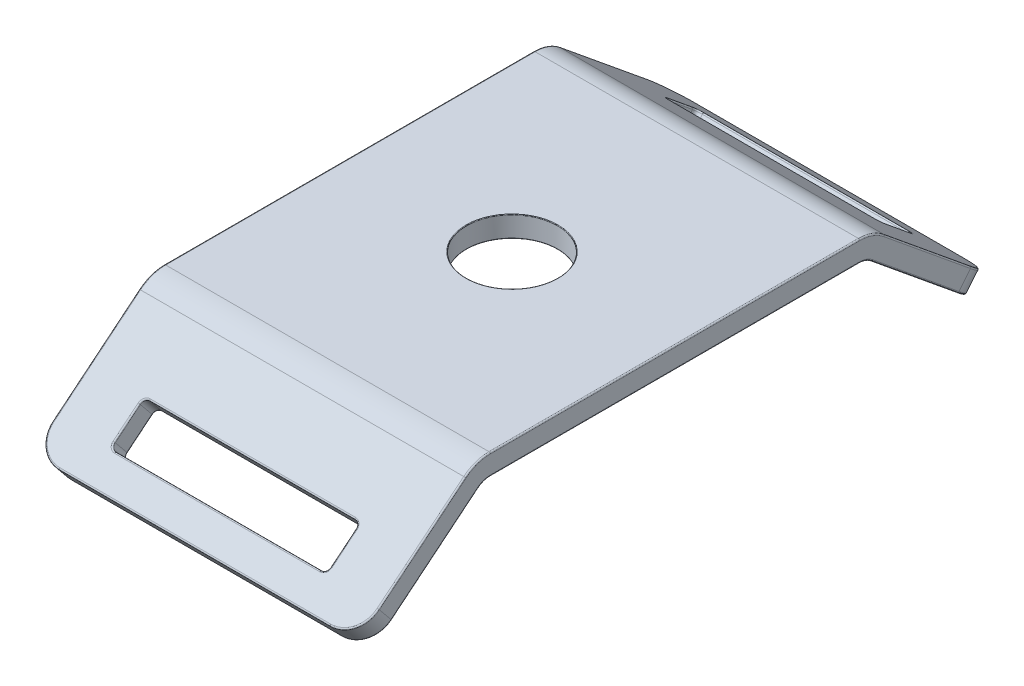
SolidWorks part; units mm, degrees
ref_plane "Front Plane" through (0, 0, 0) normal (0, 0, 1) x (1, 0, 0)
ref_plane "Top Plane" through (0, 0, 0) normal (0, 1, 0) x (1, 0, 0)
ref_plane "Right Plane" through (0, 0, 0) normal (1, 0, 0) x (0, 0, -1)
sketch "Sketch1" plane through (0, 0, 0) normal (0, 0, 1) x (1, 0, 0)
  line L0 (-7.5, 0) -> (7.5, 0) construction
  line L1 (0, 2.6) -> (0, -2.6) construction
  dimension "Overall Width" = 15
  dimension "Overall Height" = 5.2
sketch "Sketch2" plane through (0, 0, 0) normal (0, 1, 0) x (1, 0, 0)
  line L0 (0, 14.6) -> (0, -14.6) construction
  circle A0 centre (0, 0) radius 2.1 construction
  dimension "Mounting Hole Diameter" = 4.2
  dimension "Overall Length" = 29.2
sketch "Sketch3" plane through (0, 0, 0) normal (1, 0, 0) x (0, 0, -1)
  line L10 (-14.5767, -1.8387) -> (-9.6582, 2.1865)
  line L13 (-8.5, 2.6) -> (8.5, 2.6)
  line L14 (0, 2.6) -> (0, -2.6) construction
  line L15 (-13.9654, -2.5856) -> (-9.061, 1.428)
  line L16 (-8.4819, 1.6348) -> (8.4819, 1.6348)
  line L17 (-14.5856, -1.928) -> (-14.0548, -2.5767)
  line L18 (-13.4596, -2.1717) -> (-8.8083, 1.6348) construction
  line L19 (-14.0709, -1.4247) -> (-9.1529, 2.6) construction
  line L20 (-14.6, 2.6) -> (-14.6, -2.6) construction
  line L21 (-14.6, -2.6) -> (0, -2.6) construction
  line L22 (-9.1529, 2.6) -> (0, 2.6) construction
  line L23 (-8.8083, 1.6348) -> (0, 1.6348) construction
  line L24 (0, 2.6) -> (0, -2.6) construction
  line L25 (14.5767, -1.8387) -> (9.6582, 2.1865)
  line L26 (14.5856, -1.928) -> (14.0548, -2.5767)
  line L27 (13.9654, -2.5856) -> (9.061, 1.428)
  arc A0 (-13.9654, -2.5856) -> (-14.0548, -2.5767) centre (-14.0056, -2.5365) cw
  arc A1 (-14.5767, -1.8387) -> (-14.5856, -1.928) centre (-14.5365, -1.8878) ccw
  arc A2 (-9.6582, 2.1865) -> (-8.5, 2.6) centre (-8.5, 0.7712) cw
  arc A3 (-9.061, 1.428) -> (-8.4819, 1.6348) centre (-8.4819, 0.7204) cw
  arc A4 (9.061, 1.428) -> (8.4819, 1.6348) centre (8.4819, 0.7204) ccw
  arc A5 (9.6582, 2.1865) -> (8.5, 2.6) centre (8.5, 0.7712) ccw
  arc A6 (14.5767, -1.8387) -> (14.5856, -1.928) centre (14.5365, -1.8878) cw
  arc A7 (13.9654, -2.5856) -> (14.0548, -2.5767) centre (14.0056, -2.5365) ccw
  dimension "D2" = 0.0635
  dimension "D3" = 1.8288
  dimension "D4" = 0.9144
  dimension "D5" = 8.5
  dimension "D1" = 0.9652
extrude "Boss-Extrude1" add sketch "Sketch3" along normal up to vertex (7.5 mm away) and the other way up to vertex (7.5 mm away) up to point (7.5, 0, 0) other way up to point (-7.5, 0, 0)
fillet "Fillet4" radius 1.27 4 edges at (-7.5, -2.2524, 14.3202) (7.5, -2.2524, 14.3202) (7.5, -2.2524, -14.3202) (-7.5, -2.2524, -14.3202)
fillet "Fillet2" radius 0.0635 28 edges at (-7.5, -0.1967, 11.0464) (-7.5, 1.5816, 8.7893) (-7.5, 1.6348, 0) (-7.5, 1.5816, -8.7893) (-7.5, -0.1967, -11.0464) (-7.5, 0.5559, -11.6506) (-7.5, 2.4935, -9.1149) (-7.5, 2.6, 0) (-7.5, 2.4935, 9.1149) (-7.5, 0.5559, 11.6506) (7.5, 0.5559, 11.6506) (7.5, 2.4935, 9.1149) (7.5, 2.6, 0) (7.5, 2.4935, -9.1149) (7.5, 0.5559, -11.6506) (7.5, -0.1967, -11.0464) (7.5, 1.5816, -8.7893) (7.5, 1.6348, 0) (7.5, 1.5816, 8.7893) (7.5, -0.1967, 11.0464) (-7.2587, -1.5462, -14.2194) (-7.2587, -1.5462, 14.2194) (-7.2587, -2.2932, 13.6081) (-7.2587, -2.2932, -13.6081) (7.2587, -2.2932, 13.6081) (7.2587, -2.2932, -13.6081) (7.2587, -1.5462, -14.2194) (7.2587, -1.5462, 14.2194)
sketch "Sketch4" plane through (0, 2.6, 0) normal (0, 1, 0) x (1, 0, 0)
  circle A0 centre (0, 0) radius 2.1 construction
  circle A1 centre (0, 0) radius 2.1
extrude "Cut-Extrude1" cut sketch "Sketch4" against normal through all both and the other way through all
fillet "Fillet1" radius 0.0254 2 edges at (0, 1.6348, 2.1) (0, 2.6, -2.1)
sketch "Sketch6" plane through (0, 3.7235, -7.7801) normal (0, -0.7739, 0.6333) x (1, 0, 0)
  line L0 (0, 5.3093) -> (0, 2.016) construction
  line L1 (4.721, -7.416) -> (-4.721, -7.416)
  line L2 (4.975, -7.162) -> (4.975, -5.67)
  line L3 (4.721, -5.416) -> (-4.721, -5.416)
  line L4 (-4.975, -7.162) -> (-4.975, -5.67)
  line L5 (4.975, -7.416) -> (-4.975, -5.416) construction
  line L6 (4.975, -5.416) -> (-4.975, -7.416) construction
  line L7 (0, -7.636) -> (0, 14.9614) construction
  line L8 (6.23, -8.846) -> (-6.23, -8.846) construction
  arc A0 (-4.721, -7.416) -> (-4.975, -7.162) centre (-4.721, -7.162) cw
  arc A1 (-4.721, -5.416) -> (-4.975, -5.67) centre (-4.721, -5.67) ccw
  arc A2 (4.721, -7.416) -> (4.975, -7.162) centre (4.721, -7.162) ccw
  arc A3 (4.975, -5.67) -> (4.721, -5.416) centre (4.721, -5.67) ccw
  point P0 (0, -6.416)
  dimension "D3" = 0.254
  dimension "D1" = 9.95
  dimension "D2" = 2
  dimension "D4" = 1.43
extrude "Cut-Extrude2" cut sketch "Sketch6" against normal through all both and the other way through all
mirror "Mirror1" about plane through (0, 0, 0) normal (0, 0, 1) of "Cut-Extrude2"
fillet "Fillet3" radius 0.0635 32 edges at (0, -0.9732, 13.5192) (4.9006, -0.9261, 13.4616) (4.975, -0.3399, 12.7453) (4.9006, 0.2463, 12.029) (0, 0.2934, 11.9714) (-4.9006, 0.2463, 12.029) (-4.975, -0.3399, 12.7453) (-4.9006, -0.9261, 13.4616) (-4.975, -1.0869, 12.134) (-4.9006, -0.5007, 11.4177) (0, -0.4535, 11.3601) (4.9006, -0.5007, 11.4177) (4.975, -1.0869, 12.134) (4.9006, -1.6731, 12.8503) (0, -1.7202, 12.9079) (-4.9006, -1.6731, 12.8503) (4.9006, -1.6731, -12.8503) (4.975, -1.0869, -12.134) (4.9006, -0.5007, -11.4177) (0, -0.4535, -11.3601) (-4.9006, -0.5007, -11.4177) (-4.975, -1.0869, -12.134) (-4.9006, -1.6731, -12.8503) (0, -1.7202, -12.9079) (-4.9006, 0.2463, -12.029) (0, 0.2934, -11.9714) (4.9006, 0.2463, -12.029) (4.975, -0.3399, -12.7453) (4.9006, -0.9261, -13.4616) (0, -0.9732, -13.5192) (-4.9006, -0.9261, -13.4616) (-4.975, -0.3399, -12.7453)
sketch "Sketch5" plane through (0, 2.6, 0) normal (0, 1, 0) x (1, 0, 0)
  line L0 (0, 0) -> (1.4849, -1.4849) construction
  line L1 (0, 0) -> (2.1, 0) construction
  line L2 (0, 0) -> (-1.4849, -1.4849) construction
  line L3 (0, 0) -> (-1.4849, 1.4849) construction
  line L4 (0, 0) -> (1.4849, 1.4849) construction
  circle A1 centre (0, 0) radius 2.1 construction
  point P7 (1.4849, -1.4849)
  point P8 (-1.4849, -1.4849)
  point P9 (-1.4849, 1.4849)
  point P12 (1.4849, 1.4849)
  dimension "D1" = 45
  dimension "D2" = 90
sketch "Sketch7" plane through (0, 0, 0) normal (1, 0, 0) x (0, 0, -1)
  line L0 (-14.0056, -2.6) -> (14.0056, -2.6) construction
  line L2 (14.6, -2.6) -> (-14.6, -2.6) construction
  line L3 (-14.6, 0) -> (-14.6, -2.6) construction
  arc A1 (9.6582, 2.1865) -> (8.5, 2.6) centre (8.5, 0.7712) ccw construction
  arc A2 (13.9654, -2.5856) -> (14.0548, -2.5767) centre (14.0056, -2.5365) ccw construction
  point P2 (8.5, 2.6)
  point P3 (-14.0056, -2.6)
  point P5 (14.0056, -2.6)
  point P11 (0, -2.6)
  point P13 (0, -2.6)
  point P22 (-14.6, -2.6)
  point P23 (14.6, -2.6)
sketch "Sketch8" plane through (0, 0, 0) normal (0, 1, 0) x (1, 0, 0)
  point P0 (-7.5, 13.6028)
  point P1 (7.5, 13.6028)
